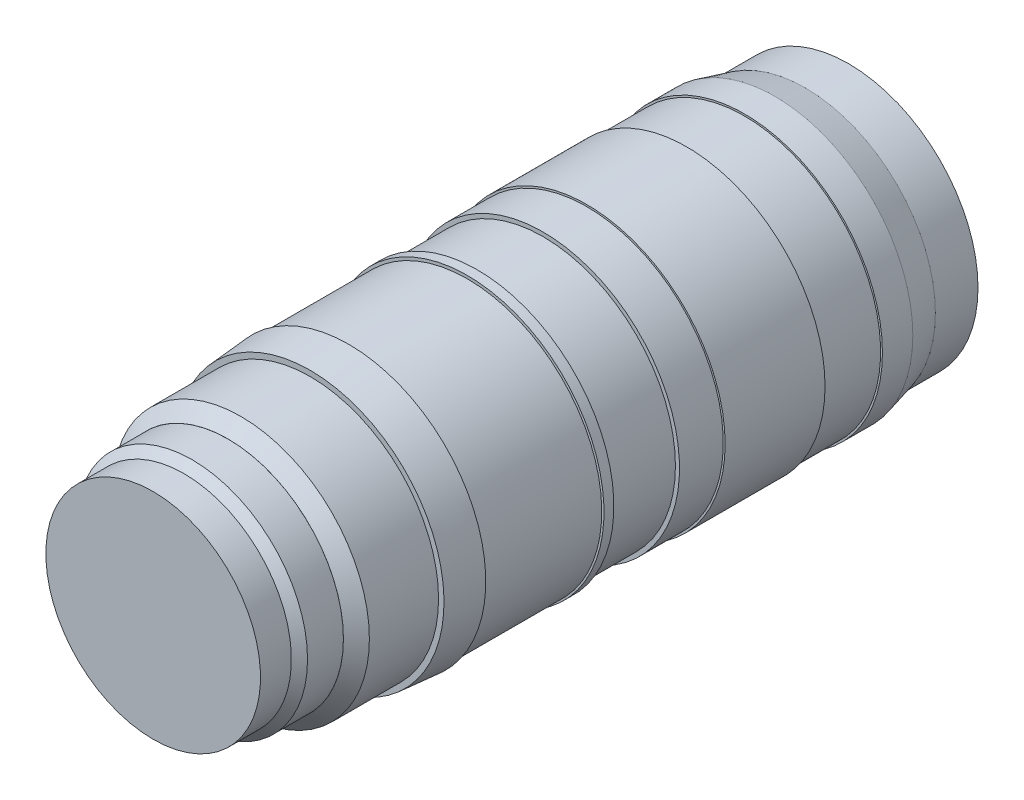
SolidWorks part; units mm, degrees
ref_plane "Front Plane" through (0, 0, 0) normal (0, 0, 1) x (1, 0, 0)
ref_plane "Top Plane" through (0, 0, 0) normal (0, 1, 0) x (1, 0, 0)
ref_plane "Right Plane" through (0, 0, 0) normal (1, 0, 0) x (0, 0, -1)
sketch "Sketch1" plane through (0, 0, 0) normal (1, 0, 0) x (0, 0, -1)
  line L0 (-107.78, -0.224) -> (-203.2, -0.224)
  line L1 (-203.2, -0.224) -> (-203.2, 32.371)
  line L2 (-203.2, 32.371) -> (-193.9, 32.371)
  line L3 (-193.9, 32.371) -> (-193.9, 34.821)
  line L4 (-193.9, 34.821) -> (-180.47, 34.821)
  line L5 (-180.47, 34.821) -> (-180.47, 38.776)
  line L6 (-180.47, 38.776) -> (-155.52, 38.776)
  line L7 (-155.52, 38.776) -> (-155.52, 40.426)
  line L8 (-143.78, 41.376) -> (-155.52, 40.426)
  line L9 (-143.78, 41.376) -> (-143.78, 40.601)
  line L10 (-143.78, 40.601) -> (-107.78, 40.601)
  line L11 (-107.78, 40.601) -> (-107.78, -0.224)
  dimension "D2" = 32.595
  dimension "D3" = 9.3
  dimension "D4" = 35.045
  dimension "D5" = 13.43
  dimension "D6" = 39
  dimension "D7" = 24.95
  dimension "D8" = 40.65
  dimension "D9" = 41.6
  dimension "D10" = 11.74
  dimension "D11" = 40.825
  dimension "D12" = 36
revolve "Revolve1" add sketch "Sketch1" angle 360 about L0
chamfer "Chamfer1" distance 3.937 angle 45
chamfer "Chamfer2" distance 2.54 angle 45
sketch "Sketch2" plane through (0, 0, 0) normal (0, 1, 0) x (1, 0, 0)
  line L0 (-40.825, -107.78) -> (-41.5, -107.78)
  line L1 (-41.5, -107.78) -> (-41.5, -104.78)
  line L2 (-41.5, -104.78) -> (-40.2, -104.78)
  line L3 (-40.2, -104.78) -> (-40.2, -84.78)
  line L4 (-40.2, -84.78) -> (-41.43, -84.78)
  line L5 (-41.43, -84.78) -> (-41.43, -71.48)
  line L6 (-41.43, -71.48) -> (-42, -71.48)
  line L7 (-42, -71.48) -> (-42, -41.14)
  line L8 (-42, -41.14) -> (-41.35, -41.14)
  line L9 (-41.35, -41.14) -> (-41.35, -23.61)
  line L10 (-41.35, -23.61) -> (-41.905, -23.61)
  line L11 (-41.905, -23.61) -> (-41.905, -14.39)
  line L12 (-41.905, -14.39) -> (-39.5, -5.13)
  line L13 (-39.5, -5.13) -> (0, -5.13)
  line L14 (0, -5.13) -> (0, -107.78)
  line L15 (40.825, -107.78) -> (-40.825, -107.78) construction
  line L16 (0, -107.78) -> (-40.825, -107.78)
  dimension "D1" = 41.5
  dimension "D2" = 3
  dimension "D3" = 40.2
  dimension "D4" = 20
  dimension "D5" = 41.43
  dimension "D6" = 13.3
  dimension "D7" = 42
  dimension "D8" = 30.34
  dimension "D9" = 41.35
  dimension "D10" = 17.53
  dimension "D11" = 41.905
  dimension "D12" = 9.22
  dimension "D13" = 39.5
  dimension "D14" = 9.26
revolve "Revolve2" add sketch "Sketch2" angle 360 about L14
sketch "Sketch3" plane through (0, 0, 5.13) normal (0, 0, -1) x (-1, 0, 0)
  circle A0 centre (0, 0) radius 39.2929
extrude "Boss-Extrude1" add sketch "Sketch3" along normal blind 13.15
sketch "Sketch4" plane through (0, 0, -8.02) normal (0, 0, -1) x (-1, 0, 0)
  circle A0 centre (0, 0) radius 37.6487
extrude "Cut-Extrude1" cut sketch "Sketch4" against normal blind 2
